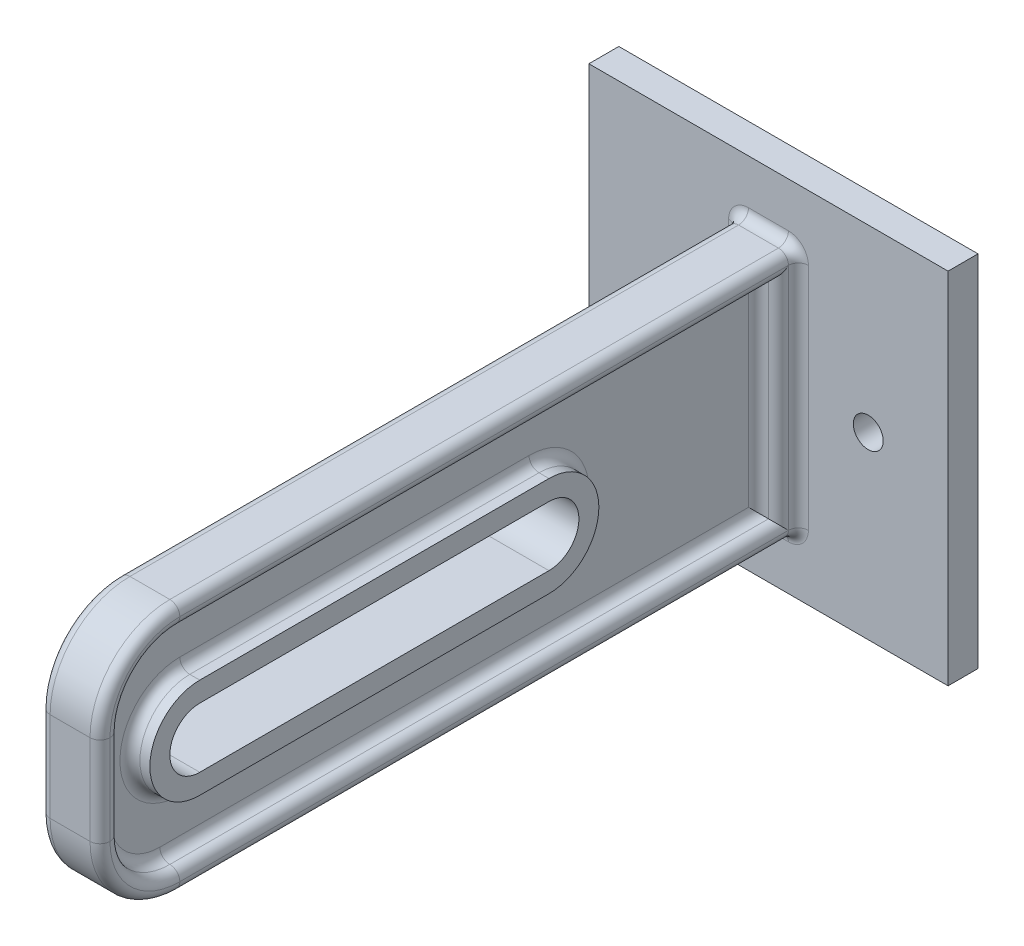
SolidWorks part; units mm, degrees
ref_plane "Front Plane" through (0, 0, 0) normal (0, 0, 1) x (1, 0, 0)
ref_plane "Top Plane" through (0, 0, 0) normal (0, 1, 0) x (1, 0, 0)
ref_plane "Right Plane" through (0, 0, 0) normal (1, 0, 0) x (0, 0, -1)
sketch "Sketch1" plane through (0, 0, 0) normal (0, 0, 1) x (1, 0, 0)
  line L1 (-18, -18) -> (18, -18)
  line L2 (-18, -18) -> (-18, 18)
  line L3 (-18, 18) -> (18, 18)
  line L4 (18, -18) -> (18, 18)
  line L5 (-18, -18) -> (18, 18) construction
  line L6 (-18, 18) -> (18, -18) construction
  point P0 (0, 0)
  dimension "D1" = 36
  dimension "D2" = 36
extrude "Boss-Extrude1" add sketch "Sketch1" along normal blind 3
sketch "Sketch2" plane through (0, 0, 3) normal (0, 0, 1) x (1, 0, 0)
  line L0 (0, 13.5997) -> (0, -10.3529) construction
  circle A0 centre (-10, 0) radius 1.5
  circle A1 centre (10, 0) radius 1.5
  dimension "D1" = 3
  dimension "D2" = 3
  dimension "D3" = 20
extrude "Cut-Extrude1" cut sketch "Sketch2" against normal through all
sketch "Sketch3" plane through (0, 0, 3) normal (0, 0, 1) x (1, 0, 0)
  line L1 (-3, -12.5) -> (3, -12.5)
  line L2 (-3, -12.5) -> (-3, 12.5)
  line L3 (-3, 12.5) -> (3, 12.5)
  line L4 (3, -12.5) -> (3, 12.5)
  line L5 (-3, -12.5) -> (3, 12.5) construction
  line L6 (-3, 12.5) -> (3, -12.5) construction
  point P0 (0, 0)
  dimension "D1" = 25
  dimension "D2" = 6
extrude "Boss-Extrude2" add sketch "Sketch3" along normal blind 70
sketch "Sketch5" plane through (3, 0, 0) normal (1, 0, 0) x (0, 0, -1)
  line L0 (-63, 0) -> (-28, 0) construction
  line L1 (-63, 3) -> (-28, 3)
  line L2 (-63, -3) -> (-28, -3)
  line L4 (-73, -12.5) -> (-73, 12.5) construction
  arc A0 (-63, 3) -> (-63, -3) centre (-63, 0) ccw
  arc A1 (-28, -3) -> (-28, 3) centre (-28, 0) ccw
  point P3 (-45.5, 0)
  dimension "D1" = 3
  dimension "D2" = 35
  dimension "D3" = 10
extrude "Cut-Extrude2" cut sketch "Sketch5" against normal through all
fillet "Fillet1" radius 8 2 edges at (0, 12.5, 73) (0, -12.5, 73)
sketch "Sketch6" plane through (3, 0, 0) normal (1, 0, 0) x (0, 0, -1)
  line L8 (-5, 10.5) -> (-65, 10.5)
  line L9 (-71, 4.5) -> (-71, -4.5)
  line L10 (-65, -10.5) -> (-5, -10.5)
  line L11 (-5, -10.5) -> (-5, 10.5)
  line L12 (-5, 10.5) -> (-65, 10.5)
  line L13 (-71, 4.5) -> (-71, -4.5)
  line L14 (-65, -10.5) -> (-5, -10.5)
  line L15 (-5, -10.5) -> (-5, 10.5)
  line L20 (-28, 5) -> (-63, 5)
  line L21 (-63, -5) -> (-28, -5)
  line L22 (-28, 5) -> (-63, 5)
  line L23 (-63, -5) -> (-28, -5)
  arc A4 (-65, 10.5) -> (-71, 4.5) centre (-65, 4.5) ccw
  arc A5 (-71, -4.5) -> (-65, -10.5) centre (-65, -4.5) ccw
  arc A6 (-65, 10.5) -> (-71, 4.5) centre (-65, 4.5) ccw
  arc A7 (-71, -4.5) -> (-65, -10.5) centre (-65, -4.5) ccw
  arc A12 (-28, -5) -> (-28, 5) centre (-28, 0) ccw
  arc A13 (-63, 5) -> (-63, -5) centre (-63, 0) ccw
  arc A14 (-28, -5) -> (-28, 5) centre (-28, 0) ccw
  arc A15 (-63, 5) -> (-63, -5) centre (-63, 0) ccw
  dimension "D1" = 2
  dimension "D2" = 2
extrude "Cut-Extrude3" cut sketch "Sketch6" against normal blind 2
mirror "Mirror1" about plane through (0, 0, 0) normal (1, 0, 0) of "Cut-Extrude3"
fillet "Fillet2" radius 1 12 edges at (-1, -10.5, 35) (-1, -8.7426, 69.2426) (-1, 0, 71) (-1, 8.7426, 69.2426) (-1, 10.5, 35) (-1, 0, 5) (1, 10.5, 35) (1, 8.7426, 69.2426) (1, 0, 71) (1, -8.7426, 69.2426) (1, 0, 5) (1, -10.5, 35)
fillet "Fillet3" radius 1 8 edges at (-1, 5, 45.5) (-1, 0, 23) (-1, -5, 45.5) (-1, 0, 68) (1, 5, 45.5) (1, 0, 23) (1, -5, 45.5) (1, 0, 68)
fillet "Fillet4" radius 1 10 edges at (-3, 12.5, 34) (-3, 10.1569, 70.6569) (-3, -12.5, 34) (-3, -10.1569, 70.6569) (-3, 0, 73) (3, -12.5, 34) (3, -10.1569, 70.6569) (3, 12.5, 34) (3, 10.1569, 70.6569) (3, 0, 73)
fillet "Fillet6" radius 1 11 edges at (-3, -10.5, 35) (-3, -8.7426, 69.2426) (-3, 0, 71) (-3, 8.7426, 69.2426) (-3, 10.5, 35) (-3, 0, 5) (3, 10.5, 35) (3, 8.7426, 69.2426) (3, -10.5, 35) (3, -8.7426, 69.2426) (3, 0, 71)
fillet "Fillet5" radius 1 8 edges at (0, 12.5, 3) (-2.7071, 12.2071, 3) (0, -12.5, 3) (-2.7071, -12.2071, 3) (-3, 0, 3) (2.7071, 12.2071, 3) (3, 0, 3) (2.7071, -12.2071, 3)
fillet "Fillet9" radius 1 1 edges at (3, 0, 5)
